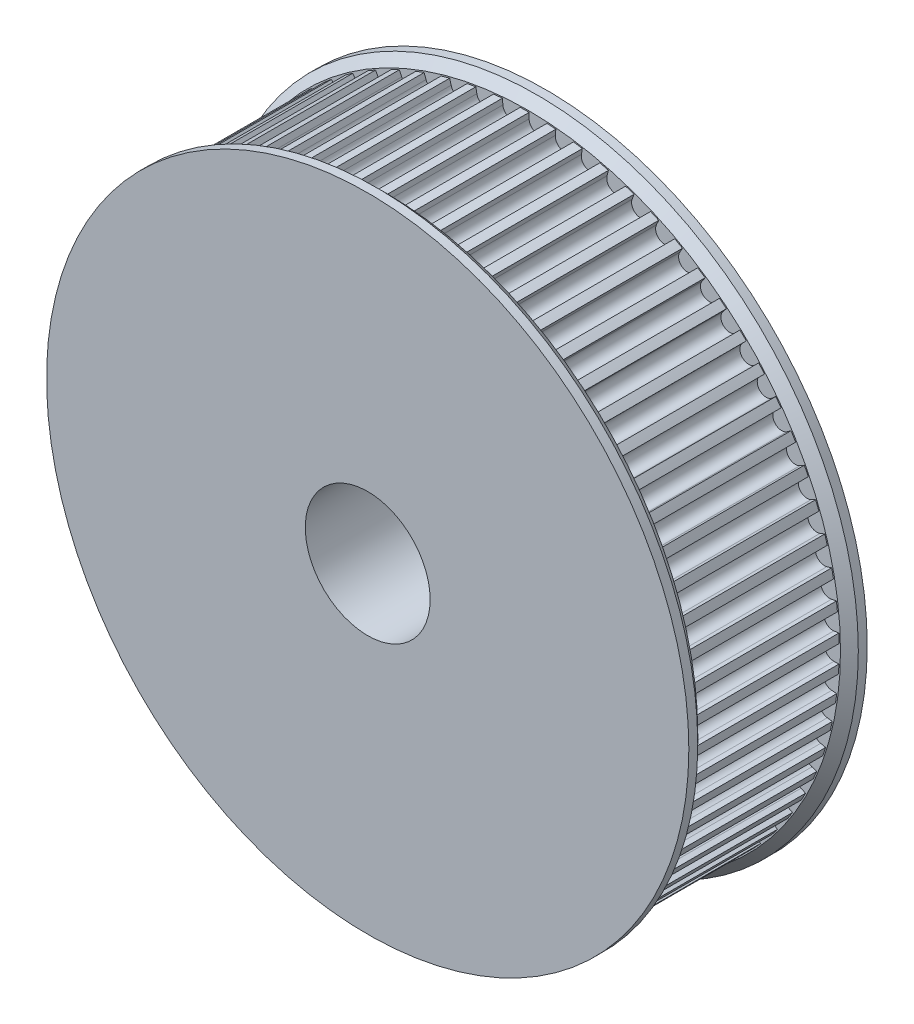
SolidWorks part; units mm, degrees
material "PA Type 6"
ref_plane "Front Plane" through (0, 0, 0) normal (0, 0, 1) x (1, 0, 0)
ref_plane "Top Plane" through (0, 0, 0) normal (0, 1, 0) x (1, 0, 0)
ref_plane "Right Plane" through (0, 0, 0) normal (1, 0, 0) x (0, 0, -1)
sketch "Sketch1" plane through (0, 0, 0) normal (0, 0, 1) x (1, 0, 0)
  circle A0 centre (0, 0) radius 18
extrude "Boss-Extrude1" add sketch "Sketch1" along normal blind 20
sketch "Sketch2" plane through (0, 0, 20) normal (0, 0, 1) x (1, 0, 0)
  circle A0 centre (0, 0) radius 7
extrude "Cut-Extrude1" cut sketch "Sketch2" against normal blind 60
sketch "Sketch4" plane through (0, 0, 20) normal (0, 0, 1) x (1, 0, 0)
  circle A0 centre (0, 0) radius 14.576
  circle A1 centre (0, 0) radius 34.85
  dimension "D1" = 69.7
extrude "Boss-Extrude2" add sketch "Sketch4" against normal blind 17
sketch "Sketch6" plane through (0, 0, 20) normal (0, 0, 1) x (1, 0, 0)
  line L0 (1.0951, 35.4896) -> (1.0951, 34.2265) construction
  line L1 (2.0951, 35.4896) -> (2.0951, 34.2265)
  line L2 (0.0951, 35.4896) -> (0.0951, 34.2265)
  arc A0 (2.0951, 35.4896) -> (0.0951, 35.4896) centre (1.0951, 35.4896) ccw
  arc A1 (0.0951, 34.2265) -> (2.0951, 34.2265) centre (1.0951, 34.2265) ccw
  point P2 (1.0951, 34.858)
  point P7 (1.0951, 34.2265)
  dimension "D1" = 1
extrude "Cut-Extrude3" cut sketch "Sketch6" against normal blind 18
pattern_circular "CirPattern1" count 73 over 360 about axis through (0, 0, 20) along (0, 0, 1) of "Cut-Extrude3"
sketch "Sketch7" plane through (0, 0, 20) normal (0, 0, 1) x (1, 0, 0)
  circle A0 centre (0, 0) radius 7
  circle A1 centre (0, 0) radius 36
extrude "Boss-Extrude3" add sketch "Sketch7" along normal blind 2
pattern_linear "LPattern1" count 2 spacing 18 along (0, 0, -1) of "Boss-Extrude3"
chamfer "Chamfer1" distance 1 angle 45 2 edges at (36, 0, 20) (36, 0, 4)
sketch "Sketch5" plane through (0, 0, 20) normal (0, 0, 1) x (1, 0, 0)
  circle A0 centre (0.7243, 29.1419) radius 2.8029
extrude "Cut-Extrude2" cut sketch "Sketch5" against normal blind 4
